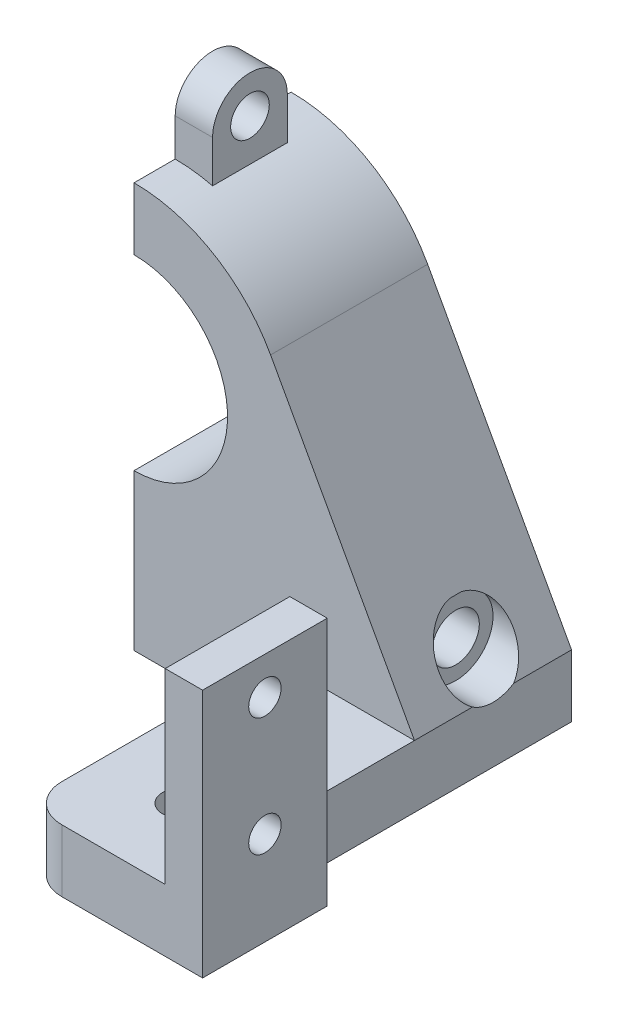
SolidWorks part; units mm, degrees
ref_plane "前视基准面" through (0, 0, 0) normal (0, 0, 1) x (1, 0, 0)
ref_plane "上视基准面" through (0, 0, 0) normal (0, 1, 0) x (1, 0, 0)
ref_plane "右视基准面" through (0, 0, 0) normal (1, 0, 0) x (0, 0, -1)
other "Configuration Table"
sketch "草图1" plane through (0, 0, 0) normal (0, 0, 1) x (1, 0, 0)
  line L0 (-10.9562, 6.0176) -> (-22.5, -15)
  line L1 (-22.5, -15) -> (-22.5, -20)
  line L2 (-22.5, -20) -> (22.5, -20)
  line L3 (0, 0) -> (0, -50000) construction
  line L4 (22.5, -15) -> (22.5, -20)
  line L5 (10.9562, 6.0176) -> (22.5, -15)
  circle A0 centre (0, 0) radius 7.5
  arc A1 (10.9562, 6.0176) -> (-10.9562, 6.0176) centre (0, 0) ccw
  point P11 (0, -20)
  dimension "D1" = 25
  dimension "D2" = 15
  dimension "D3" = 45
  dimension "D4" = 5
  dimension "D5" = 20
extrude "凸台-拉伸1" add sketch "草图1" along normal blind 12.6
sketch "草图2" plane through (0, 0, 0) normal (0, 0, 1) x (1, 0, 0)
  line L0 (-22.5, -15) -> (-11.2083, -15)
  line L1 (-11.2083, -15) -> (-11.2083, -20)
  line L2 (-22.5, -20) -> (22.5, -20) construction
  line L3 (-11.2083, -20) -> (-22.5, -20)
  line L4 (-22.5, -20) -> (-22.5, -15)
  line L5 (0, 0) -> (0, -50000) construction
  line L6 (22.5, -20) -> (22.5, -15)
  line L7 (11.2083, -20) -> (22.5, -20)
  line L8 (11.2083, -15) -> (11.2083, -20)
  line L9 (22.5, -15) -> (11.2083, -15)
extrude "凸台-拉伸2" add sketch "草图2" along normal blind 32.6
sketch "草图3" plane through (0, 0, 0) normal (0, 1, 0) x (1, 0, 0)
  line L0 (0, 0) -> (0, -50000) construction
  line L1 (-11.2083, -32.6) -> (-22.5, -32.6) construction
  circle A0 centre (-17.5, -26.3) radius 1.5
  circle A1 centre (17.5, -26.3) radius 1.5
  dimension "D1" = 3
  dimension "D2" = 6.3
  dimension "D3" = 35
extrude "切除-拉伸1" cut sketch "草图3" against normal through all
fillet "圆角1" radius 3 3 edges at (11.2083, -17.5, 32.6) (-11.2083, -17.5, 32.6) (-22.5, -17.5, 32.6)
sketch "草图4" plane through (0, 0, 0) normal (0, 1, 0) x (1, 0, 0)
  line L0 (22.5, -22.6) -> (22.5, -32.6)
  line L1 (22.5, -32.6) -> (22.5, -12.6) construction
  line L2 (22.5, -32.6) -> (25.5, -32.6)
  line L3 (25.5, -32.6) -> (25.5, -22.6)
  line L4 (25.5, -22.6) -> (22.5, -22.6)
  dimension "D1" = 3
  dimension "D2" = 10
extrude "凸台-拉伸3" add sketch "草图4" against normal through all
sketch "草图5" plane through (0, 0, 0) normal (1, 0, 0) x (0, 0, -1)
  line L0 (-27.6, 0) -> (-27.6, -50000) construction
  line L1 (-32.6, 0) -> (-22.6, 0) construction
  circle A0 centre (-27.6, -3) radius 1.3
  circle A1 centre (-27.6, -12.5) radius 1.3
  point P4 (-27.6, 0)
  dimension "D1" = 2.6
  dimension "D2" = 2.6
  dimension "D3" = 9.5
  dimension "D4" = 0
  dimension "D5" = 3
extrude "切除-拉伸2" cut sketch "草图5" along normal through all
sketch "草图6" plane through (0, 0, 0) normal (1, 0, 0) x (0, 0, -1)
  line L1 (-33.9843, 13.7664) -> (1.3097, 13.7664)
  line L2 (-33.9843, 13.7664) -> (-33.9843, -21.1918)
  line L3 (-33.9843, -21.1918) -> (1.3097, -21.1918)
  line L4 (1.3097, 13.7664) -> (1.3097, -21.1918)
extrude "切除-拉伸3" cut sketch "草图6" against normal through all
sketch "草图7" plane through (0, 0, 0) normal (1, 0, 0) x (0, 0, -1)
  line L0 (-9.3, 12.5) -> (-9.3, 15.5)
  line L1 (0, 12.5) -> (-12.6, 12.5) construction
  line L2 (-9.3, 15.5) -> (-3.3, 15.5)
  line L3 (-3.3, 15.5) -> (-3.3, 12.5)
  line L4 (-3.3, 12.5) -> (-9.3, 12.5)
  line L5 (-6.3, 6.0176) -> (-6.3, -49993.9824) construction
  line L6 (-12.6, 6.0176) -> (0, 6.0176) construction
  line L7 (-9.3, 12.5) -> (-9.3, 9.1529)
  line L8 (-9.3, 9.1529) -> (-3.3, 9.1529)
  line L9 (-3.3, 9.1529) -> (-3.3, 12.5)
  arc A0 (-9.3, 15.5) -> (-3.3, 15.5) centre (-6.3, 15.5) cw
  circle A1 centre (-6.3, 15.5) radius 1.55
  point P11 (-6.3, 6.0176)
  point P12 (-6.3, 12.5)
  dimension "D1" = 3
  dimension "D3" = 3.1
  dimension "D2" = 3
extrude "凸台-拉伸4" add sketch "草图7" along normal blind 3 contours L5 L4 L7 L8 | A1 L5 L4 L3 L2 | L5 A1 L2 L0 L4 | L5 A0 L2 A1 | A0 L5 A1 L2 | L4 L5 L8 L9 region at (0, 13.7766, 6.3) region at (0, 10.8265, 6.3) region at (0, 18.4329, 6.3)
sketch "草图8" plane through (0, 0, 0) normal (1, 0, 0) x (0, 0, -1)
  line L0 (-6.3, 6.0176) -> (-6.3, -49993.9824) construction
  line L1 (-12.6, 6.0176) -> (0, 6.0176) construction
  line L2 (0, 12.5) -> (-3.3, 12.5) construction
  circle A0 centre (-6.3, -12.5) radius 1.901
  point P6 (-6.3, 6.0176)
  dimension "D1" = 25
extrude "切除-拉伸4" cut sketch "草图8" along normal through all
ref_plane "基准面1" through (22.5, 0, 0) normal (1, 0, 0) x (0, 0, -1)
sketch "草图9" plane through (22.5, 0, 0) normal (1, 0, 0) x (0, 0, -1)
  circle A0 centre (-6.3, -12.5) radius 3
extrude "切除-拉伸5" cut sketch "草图9" against normal blind 3
